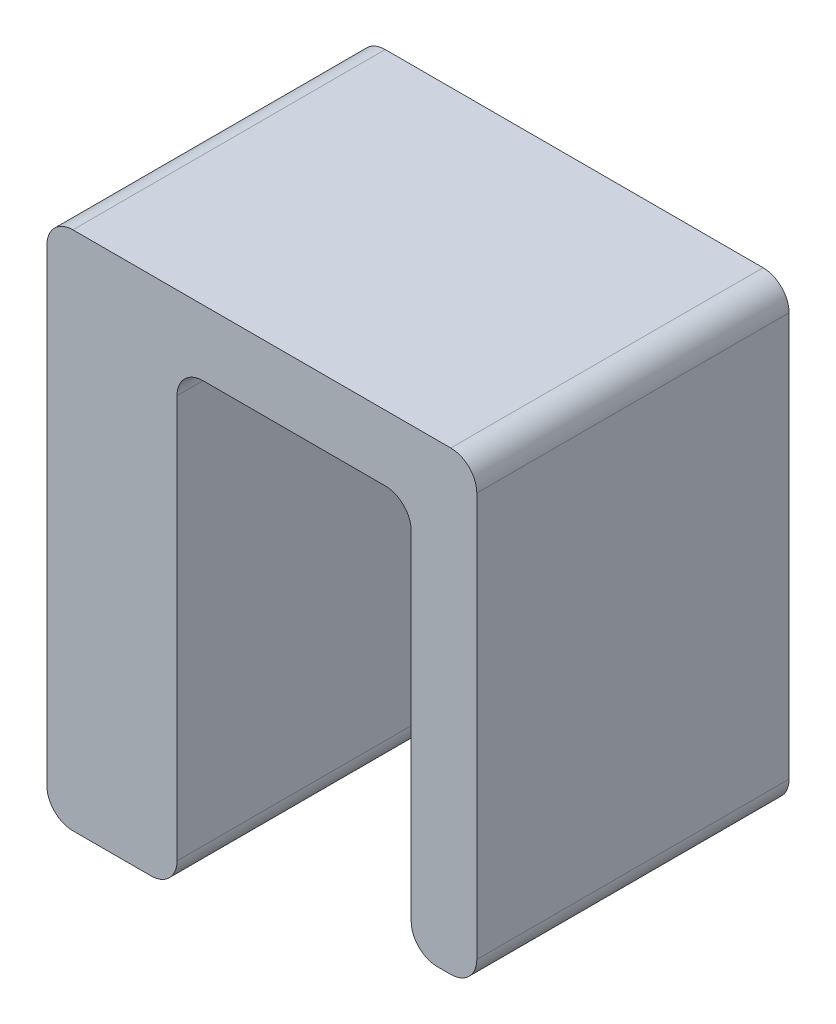
SolidWorks part; units mm, degrees
ref_plane "Front Plane" through (0, 0, 0) normal (0, 0, 1) x (1, 0, 0)
ref_plane "Top Plane" through (0, 0, 0) normal (0, 1, 0) x (1, 0, 0)
ref_plane "Right Plane" through (0, 0, 0) normal (1, 0, 0) x (0, 0, -1)
sketch "Sketch1" plane through (0, 0, 0) normal (0, 0, 1) x (1, 0, 0)
  line L0 (0, 0) -> (0, 12.7)
  line L1 (0, 12.7) -> (10.49, 12.7)
  line L2 (10.49, 12.7) -> (10.49, 1.575)
  line L3 (10.49, 1.575) -> (8.89, 1.575)
  line L4 (8.89, 1.575) -> (8.89, 11.1)
  line L5 (8.89, 11.1) -> (3.175, 11.1)
  line L6 (3.175, 11.1) -> (3.175, 0)
  line L7 (3.175, 0) -> (0, 0)
  dimension "D1" = 5.715
  dimension "D2" = 1.6
  dimension "D3" = 3.175
  dimension "D4" = 12.7
  dimension "D5" = 9.525
  dimension "D6" = 1.6
extrude "Boss-Extrude1" add sketch "Sketch1" along normal blind 7.62
fillet "Fillet1" radius 0.635 8 edges at (8.89, 11.1, 3.81) (3.175, 11.1, 3.81) (3.175, 0, 3.81) (0, 0, 3.81) (8.89, 1.575, 3.81) (10.49, 1.575, 3.81) (0, 12.7, 3.81) (10.49, 12.7, 3.81)
